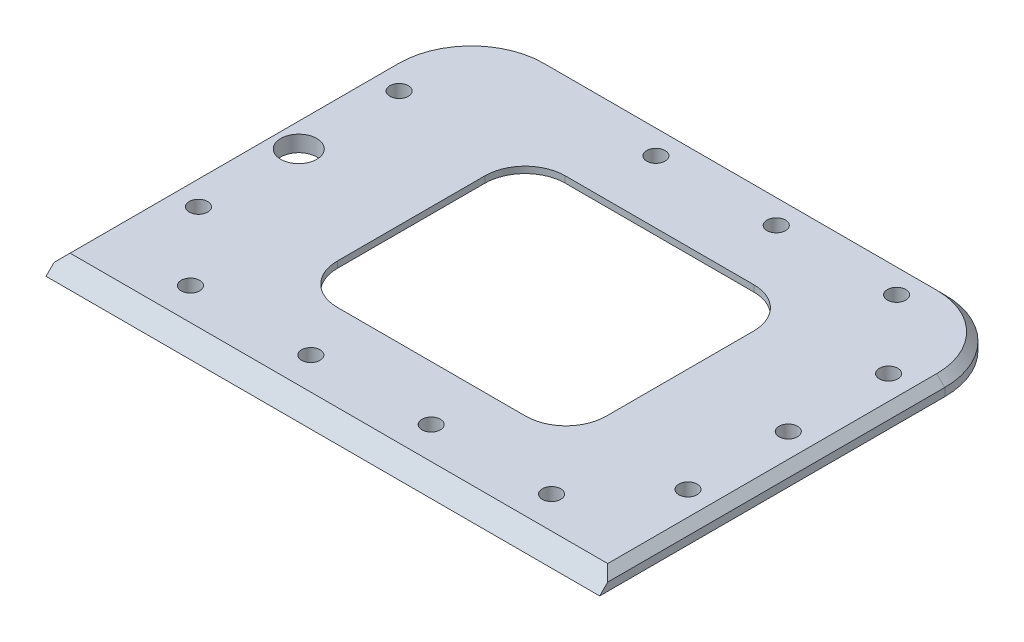
SolidWorks part; units mm, degrees
ref_plane "前视基准面" through (0, 0, 0) normal (0, 0, 1) x (1, 0, 0)
ref_plane "上视基准面" through (0, 0, 0) normal (0, 1, 0) x (1, 0, 0)
ref_plane "右视基准面" through (0, 0, 0) normal (1, 0, 0) x (0, 0, -1)
other "Configuration Table"
sketch "草图1" plane through (0, 0, 0) normal (0, 1, 0) x (1, 0, 0)
  line L0 (34.5, 51) -> (34.5, 0) construction
  line L1 (0, 0) -> (69, 0)
  line L2 (0, 0) -> (0, 51)
  line L3 (0, 51) -> (69, 51)
  line L4 (69, 0) -> (69, 51)
  line L5 (0, 25.5) -> (69, 25.5) construction
  line L6 (42, 47) -> (57, 47) construction
  line L8 (14.5, 41.7) -> (54, 41.7)
  line L9 (14.5, 41.7) -> (14.5, 9.3)
  line L10 (14.5, 9.3) -> (54, 9.3)
  line L11 (54, 41.7) -> (54, 9.3)
  circle A0 centre (4, 25.5) radius 1.15
  circle A1 centre (65, 25.5) radius 1.15
  circle A2 centre (27, 47) radius 1.15
  circle A3 centre (42, 47) radius 1.15
  circle A4 centre (42, 4) radius 1.15
  circle A5 centre (27, 4) radius 1.15
  circle A6 centre (4, 38) radius 1.15
  circle A7 centre (4, 13) radius 1.15
  circle A8 centre (65, 13) radius 1.15
  circle A9 centre (65, 38) radius 1.15
  circle A10 centre (57, 47) radius 1.15
  circle A11 centre (57, 4) radius 1.15
  circle A12 centre (12, 4) radius 1.15
  dimension "D1" = 2.3
  dimension "D2" = 61
  dimension "D3" = 15
  dimension "D4" = 43
  dimension "D7" = 25
  dimension "D8" = 15
  dimension "D9" = 10.5
  dimension "D10" = 5.3
  dimension "D5" = 69
  dimension "D6" = 51
  dimension "D11" = 11
  dimension "D12" = 5.3
extrude "凸台-拉伸1" add sketch "草图1" along normal blind 2
fillet "圆角1" radius 10 2 edges at (69, 1, -51) (0, 1, -51)
fillet "圆角2" radius 5 4 edges at (14.5, 1, -9.3) (54, 1, -9.3) (54, 1, -41.7) (14.5, 1, -41.7)
sketch "草图2" plane through (0, 2, 0) normal (0, 1, 0) x (1, 0, 0)
  line L0 (14.5, 36.7) -> (14.5, 14.3) construction
  line L1 (23.5, 39.2) -> (47, 39.2)
  line L2 (18.5, 34.2) -> (18.5, 15.8)
  line L3 (23.5, 10.8) -> (47, 10.8)
  line L4 (52, 34.2) -> (52, 15.8)
  line L5 (54, 14.3) -> (54, 36.7) construction
  line L6 (49, 41.7) -> (19.5, 41.7) construction
  line L7 (19.5, 9.3) -> (49, 9.3) construction
  line L8 (54, 14.3) -> (54, 36.7)
  line L9 (19.5, 9.3) -> (49, 9.3)
  line L10 (14.5, 36.7) -> (14.5, 14.3)
  line L11 (49, 41.7) -> (19.5, 41.7)
  arc A0 (47, 39.2) -> (52, 34.2) centre (47, 34.2) cw
  arc A1 (52, 15.8) -> (47, 10.8) centre (47, 15.8) cw
  arc A2 (23.5, 10.8) -> (18.5, 15.8) centre (23.5, 15.8) cw
  arc A3 (18.5, 34.2) -> (23.5, 39.2) centre (23.5, 34.2) cw
  arc A4 (49, 9.3) -> (54, 14.3) centre (49, 14.3) ccw construction
  arc A5 (14.5, 14.3) -> (19.5, 9.3) centre (19.5, 14.3) ccw construction
  arc A6 (19.5, 41.7) -> (14.5, 36.7) centre (19.5, 36.7) ccw construction
  arc A7 (49, 9.3) -> (54, 14.3) centre (49, 14.3) ccw
  arc A8 (14.5, 14.3) -> (19.5, 9.3) centre (19.5, 14.3) ccw
  arc A9 (19.5, 41.7) -> (14.5, 36.7) centre (19.5, 36.7) ccw
  arc A10 (54, 36.7) -> (49, 41.7) centre (49, 36.7) ccw construction
  arc A11 (54, 36.7) -> (49, 41.7) centre (49, 36.7) ccw
  dimension "D5" = 5
  dimension "D1" = 4
  dimension "D2" = 2
  dimension "D3" = 2.5
  dimension "D4" = 1.5
extrude "凸台-拉伸2" add sketch "草图2" against normal blind 0.8
sketch "草图4" plane through (69, 0, 0) normal (1, 0, 0) x (0, 0, -1)
  line L0 (0, 2) -> (-2, 0)
  line L1 (-2, 0) -> (0, 0)
  line L2 (0, 0) -> (0, 2)
  dimension "D1" = 45
extrude "凸台-拉伸4" add sketch "草图4" against normal up to surface (69 mm away) up to face at (0, 1, -20.5)
chamfer "倒角1" distance 1 angle 45 5 edges at (0, 2, -20.5) (2.9289, 2, -48.0711) (34.5, 2, -51) (66.0711, 2, -48.0711) (69, 2, -20.5)
sketch "草图3" plane through (0, 0, 0) normal (0, -1, 0) x (1, 0, 0)
  line L16 (54, -14.3) -> (54, -36.7) construction
  line L17 (49, -41.7) -> (19.5, -41.7) construction
  line L18 (14.5, -36.7) -> (14.5, -14.3) construction
  line L19 (19.5, -9.3) -> (49, -9.3) construction
  line L20 (13, -14.3) -> (13, -36.7)
  line L21 (19.5, -43.2) -> (49, -43.2)
  line L22 (55.5, -36.7) -> (55.5, -14.3)
  line L23 (49, -7.8) -> (19.5, -7.8)
  line L24 (13, -14.3) -> (13, -36.7)
  line L26 (55.5, -36.7) -> (55.5, -14.3)
  line L28 (54, -36.7) -> (54, -14.3)
  line L29 (19.5, -41.7) -> (49, -41.7)
  line L30 (14.5, -14.3) -> (14.5, -36.7)
  line L31 (49, -9.3) -> (19.5, -9.3)
  line L32 (54, -36.7) -> (54, -14.3)
  line L33 (19.5, -41.7) -> (49, -41.7)
  line L34 (14.5, -14.3) -> (14.5, -36.7)
  line L35 (49, -9.3) -> (19.5, -9.3)
  line L36 (54, -14.3) -> (54, -36.7)
  line L37 (49, -41.7) -> (19.5, -41.7)
  line L38 (14.5, -36.7) -> (14.5, -14.3)
  line L39 (19.5, -9.3) -> (49, -9.3)
  line L40 (17, -8.3) -> (51.5, -8.3)
  line L41 (17, -42.7) -> (51.5, -42.7)
  arc A20 (49, -41.7) -> (54, -36.7) centre (49, -36.7) ccw construction
  arc A21 (14.5, -36.7) -> (19.5, -41.7) centre (19.5, -36.7) ccw construction
  arc A22 (19.5, -9.3) -> (14.5, -14.3) centre (19.5, -14.3) ccw construction
  arc A23 (49, -41.7) -> (54, -36.7) centre (49, -36.7) ccw
  arc A24 (13, -36.7) -> (19.5, -43.2) centre (19.5, -36.7) ccw
  arc A25 (49, -43.2) -> (55.5, -36.7) centre (49, -36.7) ccw
  arc A26 (55.5, -14.3) -> (49, -7.8) centre (49, -14.3) ccw
  arc A27 (19.5, -7.8) -> (13, -14.3) centre (19.5, -14.3) ccw
  arc A28 (13, -36.7) -> (17, -42.7) centre (19.5, -36.7) ccw
  arc A29 (51.5, -42.7) -> (55.5, -36.7) centre (49, -36.7) ccw
  arc A30 (55.5, -14.3) -> (51.5, -8.3) centre (49, -14.3) ccw
  arc A31 (17, -8.3) -> (13, -14.3) centre (19.5, -14.3) ccw
  arc A32 (49, -41.7) -> (54, -36.7) centre (49, -36.7) ccw
  arc A33 (14.5, -36.7) -> (19.5, -41.7) centre (19.5, -36.7) ccw
  arc A34 (19.5, -9.3) -> (14.5, -14.3) centre (19.5, -14.3) ccw
  arc A35 (54, -14.3) -> (49, -9.3) centre (49, -14.3) ccw
  arc A36 (49, -41.7) -> (54, -36.7) centre (49, -36.7) ccw
  arc A37 (14.5, -36.7) -> (19.5, -41.7) centre (19.5, -36.7) ccw
  arc A38 (19.5, -9.3) -> (14.5, -14.3) centre (19.5, -14.3) ccw
  arc A39 (54, -14.3) -> (49, -9.3) centre (49, -14.3) ccw
  arc A40 (14.5, -36.7) -> (19.5, -41.7) centre (19.5, -36.7) ccw
  arc A41 (19.5, -9.3) -> (14.5, -14.3) centre (19.5, -14.3) ccw
  dimension "D3" = 1
  dimension "D4" = 1
  dimension "D1" = 1.5
  dimension "D2" = 0
extrude "凸台-拉伸3" add sketch "草图3" along normal blind 1
sketch "草图5" plane through (0, 0, 0) normal (0, -1, 0) x (1, 0, 0)
  line L0 (13, -14.3) -> (13, -36.7) construction
  line L1 (13, -16.5) -> (14.5, -16.5)
  line L2 (13, -16.5) -> (13, -34.5)
  line L3 (13, -34.5) -> (14.5, -34.5)
  line L4 (14.5, -16.5) -> (14.5, -34.5)
  line L5 (14.5, -36.7) -> (14.5, -14.3) construction
  line L6 (13, -25.5) -> (54, -25.5) construction
  line L7 (54, -14.3) -> (54, -36.7) construction
  dimension "D1" = 18
extrude "切除-拉伸1" cut sketch "草图5" along normal blind 1
chamfer "倒角2" distance 1 angle 45 2 edges at (13.75, 0, -34.5) (13.75, 0, -16.5)
sketch "草图6" plane through (0, 1.2, 0) normal (0, -1, 0) x (1, 0, 0)
  line L0 (52, -15.8) -> (52, -34.2) construction
  line L1 (47, -39.2) -> (23.5, -39.2) construction
  line L2 (18.5, -34.2) -> (18.5, -15.8) construction
  line L3 (23.5, -10.8) -> (47, -10.8) construction
  line L4 (19.5, -41.7) -> (49, -41.7)
  line L5 (54, -36.7) -> (54, -14.3)
  line L6 (49, -9.3) -> (19.5, -9.3)
  line L7 (14.5, -14.3) -> (14.5, -36.7)
  line L8 (19.5, -41.7) -> (49, -41.7)
  line L9 (54, -36.7) -> (54, -14.3)
  line L10 (49, -9.3) -> (19.5, -9.3)
  line L11 (14.5, -14.3) -> (14.5, -36.7)
  line L12 (52, -15.8) -> (52, -34.2)
  line L13 (47, -39.2) -> (23.5, -39.2)
  line L14 (18.5, -34.2) -> (18.5, -15.8)
  line L15 (23.5, -10.8) -> (47, -10.8)
  arc A0 (52, -15.8) -> (47, -10.8) centre (47, -15.8) ccw construction
  arc A1 (47, -39.2) -> (52, -34.2) centre (47, -34.2) ccw construction
  arc A2 (18.5, -34.2) -> (23.5, -39.2) centre (23.5, -34.2) ccw construction
  arc A3 (23.5, -10.8) -> (18.5, -15.8) centre (23.5, -15.8) ccw construction
  arc A4 (14.5, -36.7) -> (19.5, -41.7) centre (19.5, -36.7) ccw
  arc A5 (49, -41.7) -> (54, -36.7) centre (49, -36.7) ccw
  arc A6 (54, -14.3) -> (49, -9.3) centre (49, -14.3) ccw
  arc A7 (19.5, -9.3) -> (14.5, -14.3) centre (19.5, -14.3) ccw
  arc A8 (14.5, -36.7) -> (19.5, -41.7) centre (19.5, -36.7) ccw
  arc A9 (49, -41.7) -> (54, -36.7) centre (49, -36.7) ccw
  arc A10 (54, -14.3) -> (49, -9.3) centre (49, -14.3) ccw
  arc A11 (19.5, -9.3) -> (14.5, -14.3) centre (19.5, -14.3) ccw
  arc A12 (52, -15.8) -> (47, -10.8) centre (47, -15.8) ccw
  arc A13 (47, -39.2) -> (52, -34.2) centre (47, -34.2) ccw
  arc A14 (18.5, -34.2) -> (23.5, -39.2) centre (23.5, -34.2) ccw
  arc A15 (23.5, -10.8) -> (18.5, -15.8) centre (23.5, -15.8) ccw
  dimension "D1" = 0
sketch "草图7" plane through (0, 2, 0) normal (0, 1, 0) x (1, 0, 0)
  circle A1 centre (4, 25.5) radius 2.25
  dimension "D1" = 4.5
extrude "切除-拉伸2" cut sketch "草图7" against normal up to next
